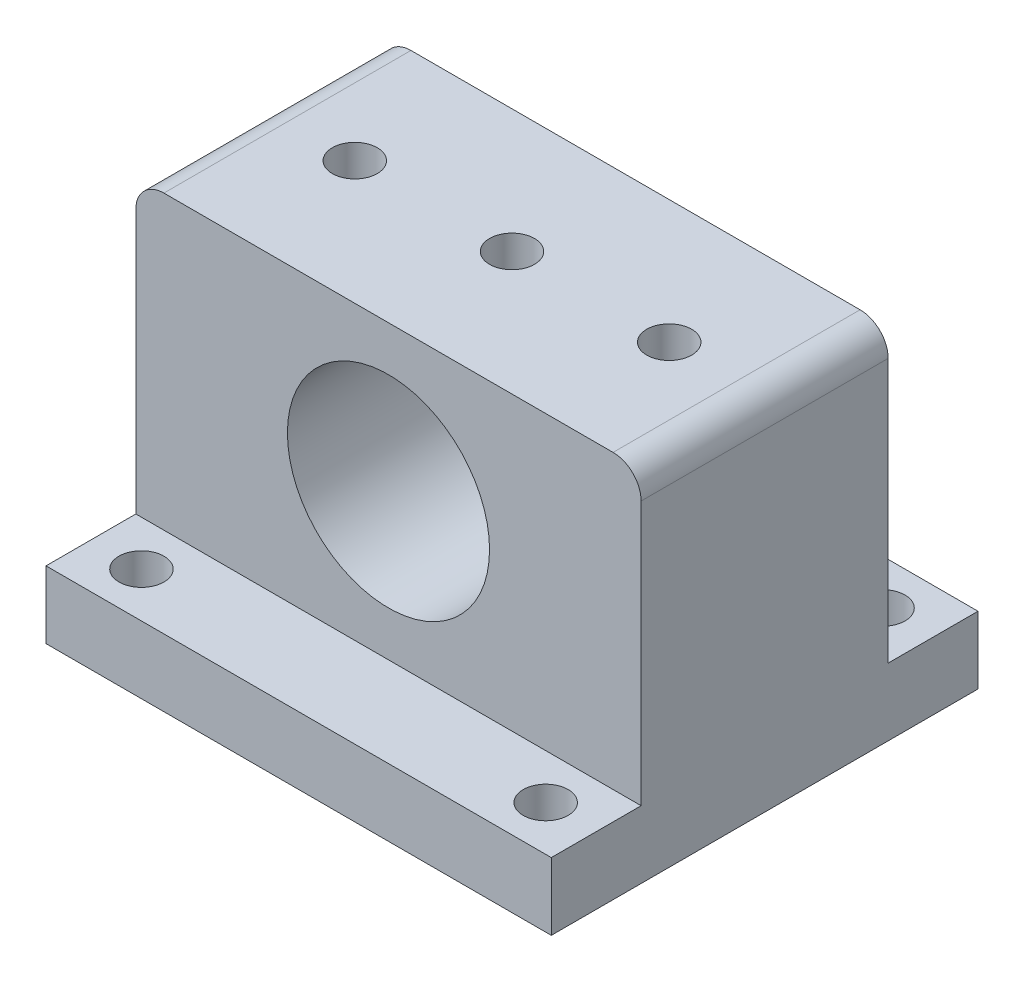
SolidWorks part; units mm, degrees
material "Alumina"
ref_plane "Front Plane" through (0, 0, 0) normal (0, 0, 1) x (1, 0, 0)
ref_plane "Top Plane" through (0, 0, 0) normal (0, 1, 0) x (1, 0, 0)
ref_plane "Right Plane" through (0, 0, 0) normal (1, 0, 0) x (0, 0, -1)
sketch "Sketch1" plane through (0, 0, 0) normal (0, 0, 1) x (1, 0, 0)
  line L0 (0, 0) -> (0, 50000) construction
  line L1 (-20, 13) -> (20, 13)
  line L2 (-22.5, 10.5) -> (-22.5, -13)
  line L3 (-22.5, -13) -> (22.5, -13)
  line L4 (22.5, 10.5) -> (22.5, -13)
  line L5 (-22.5, 13) -> (22.5, -13) construction
  line L6 (-22.5, -13) -> (22.5, 13) construction
  line L7 (0, 0) -> (50000, 0) construction
  line L9 (-22.5, -19) -> (22.5, -19)
  line L10 (-22.5, -19) -> (-22.5, -13)
  line L11 (-22.5, -13) -> (22.5, -13)
  line L12 (22.5, -19) -> (22.5, -13)
  line L13 (-22.5, -19) -> (22.5, -13) construction
  line L14 (-22.5, -13) -> (22.5, -19) construction
  arc A0 (20, 13) -> (22.5, 10.5) centre (20, 10.5) cw
  arc A1 (-20, 13) -> (-22.5, 10.5) centre (-20, 10.5) ccw
  circle A2 centre (0, 0) radius 9
  point P0 (0, 0)
  point P10 (0, -16)
  dimension "D4" = 2.5
  dimension "D5" = 18
  dimension "D1" = 45
  dimension "D2" = 26
  dimension "D3" = 6
extrude "Boss-Extrude1" add sketch "Sketch1" along normal mid plane 22 contours L1 A1 L2 L3 L4 A0 A2 region at (0, 12.4803, 0)
extrude "Boss-Extrude2" add sketch "Sketch1<3>" along normal mid plane 38 contours L9 L12 L3 L10 region at (0, -16, 0)
sketch "Sketch1<3>" plane through (0, 0, 0) normal (0, 0, 1) x (1, 0, 0) same geometry as "Sketch1"
sketch "Sketch2" plane through (0, -13, 0) normal (0, 1, 0) x (1, 0, 0)
  line L0 (0, 0) -> (0, 50000) construction
  line L1 (0, 0) -> (50000, 0) construction
  line L2 (0, -15) -> (-50000, -15) construction
  circle A0 centre (-18, -15) radius 2
  circle A1 centre (18, -15) radius 2
  circle A2 centre (18, 15) radius 2
  circle A3 centre (-18, 15) radius 2
  dimension "D2" = 4
  dimension "D1" = 15
  dimension "D3" = 18
extrude "Cut-Extrude1" cut sketch "Sketch2" against normal through all
sketch "Sketch3" plane through (0, 13, 0) normal (0, 1, 0) x (1, 0, 0)
  line L0 (0, 0) -> (0, 50000) construction
  line L1 (0, 0) -> (50000, 0) construction
  circle A0 centre (0, 0) radius 2
  circle A2 centre (-14, 0) radius 2
  dimension "D1" = 4
  dimension "D2" = 14
extrude "Cut-Extrude2" cut sketch "Sketch3" against normal up to next contours A0 region at (0, 13, 0)
cosmetic thread "Cosmetic Thread1" parameters "D2"=5
extrude "Cut-Extrude3" cut sketch "Sketch3<3>" against normal blind 20 contours A2 region at (-14, 13, 0)
sketch "Sketch3<3>" plane through (0, 13, 0) normal (0, 1, 0) x (1, 0, 0) same geometry as "Sketch3"
cosmetic thread "Cosmetic Thread2" parameters "D1"=7, "D2"=5
mirror "Mirror1" about plane through (0, 0, 0) normal (1, 0, 0) of "Cut-Extrude3"
cosmetic thread "Cosmetic Thread3" parameters "D1"=7, "D2"=5
